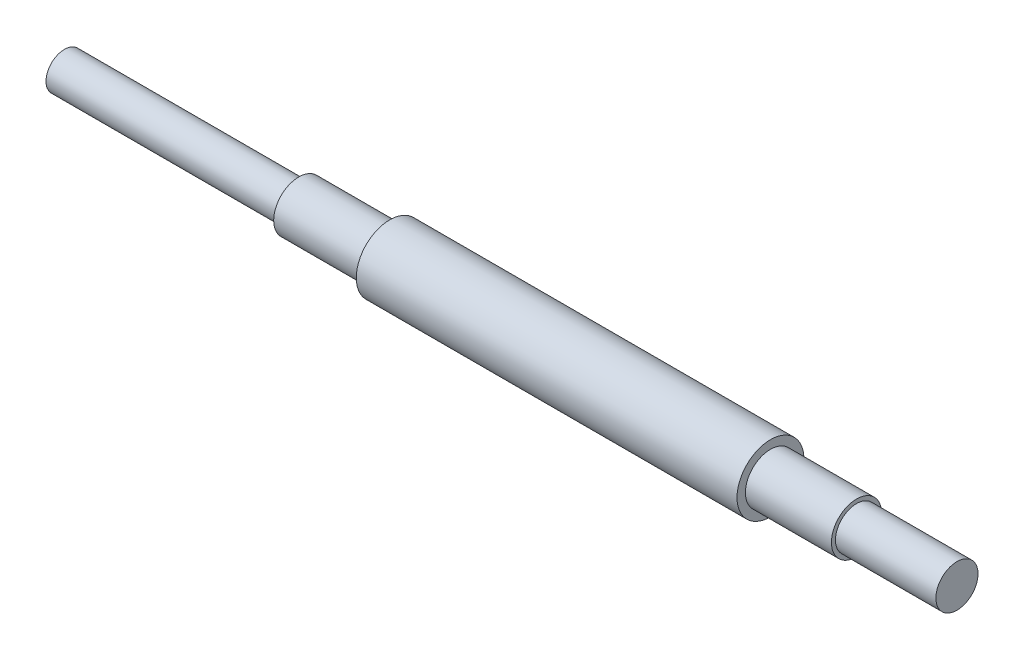
SolidWorks part; units mm, degrees
ref_plane "Front Plane" through (0, 0, 0) normal (0, 0, 1) x (1, 0, 0)
ref_plane "Top Plane" through (0, 0, 0) normal (0, 1, 0) x (1, 0, 0)
ref_plane "Right Plane" through (0, 0, 0) normal (1, 0, 0) x (0, 0, -1)
sketch "Sketch1" plane through (0, 0, 0) normal (0, 1, 0) x (1, 0, 0)
  line L0 (-78.6306, 0) -> (90.6662, 0) construction
  line L1 (-78.6306, 0) -> (-78.6306, 3.5)
  line L2 (-78.6306, 3.5) -> (-34.1806, 3.5)
  line L3 (-34.1806, 3.5) -> (-34.1806, 4.7625)
  line L4 (-34.1806, 4.7625) -> (-16.9251, 4.7625)
  line L5 (-16.9251, 4.7625) -> (-16.9251, 6.35)
  line L6 (-16.9251, 6.35) -> (55.2948, 6.35)
  line L7 (55.2948, 6.35) -> (55.2948, 4.7625)
  line L8 (55.2948, 4.7625) -> (71.6162, 4.7625)
  line L9 (71.6162, 4.7625) -> (71.6162, 3.9992)
  line L10 (71.6162, 3.9992) -> (90.6662, 3.9992)
  line L11 (90.6662, 3.9992) -> (90.6662, 0)
  line L12 (-78.6306, 0) -> (90.6662, 0)
  line L13 (-97.9506, 0) -> (194.5593, 0) construction
  dimension "D1" = 7
  dimension "D2" = 9.525
  dimension "D3" = 9.525
  dimension "D4" = 7.9985
  dimension "D5" = 44.45
  dimension "D6" = 17.2554
  dimension "D7" = 16.3214
  dimension "D8" = 19.05
  dimension "D9" = 72.22
  dimension "D10" = 6.35
revolve "Revolve1" add sketch "Sketch1" angle 360 about L13
